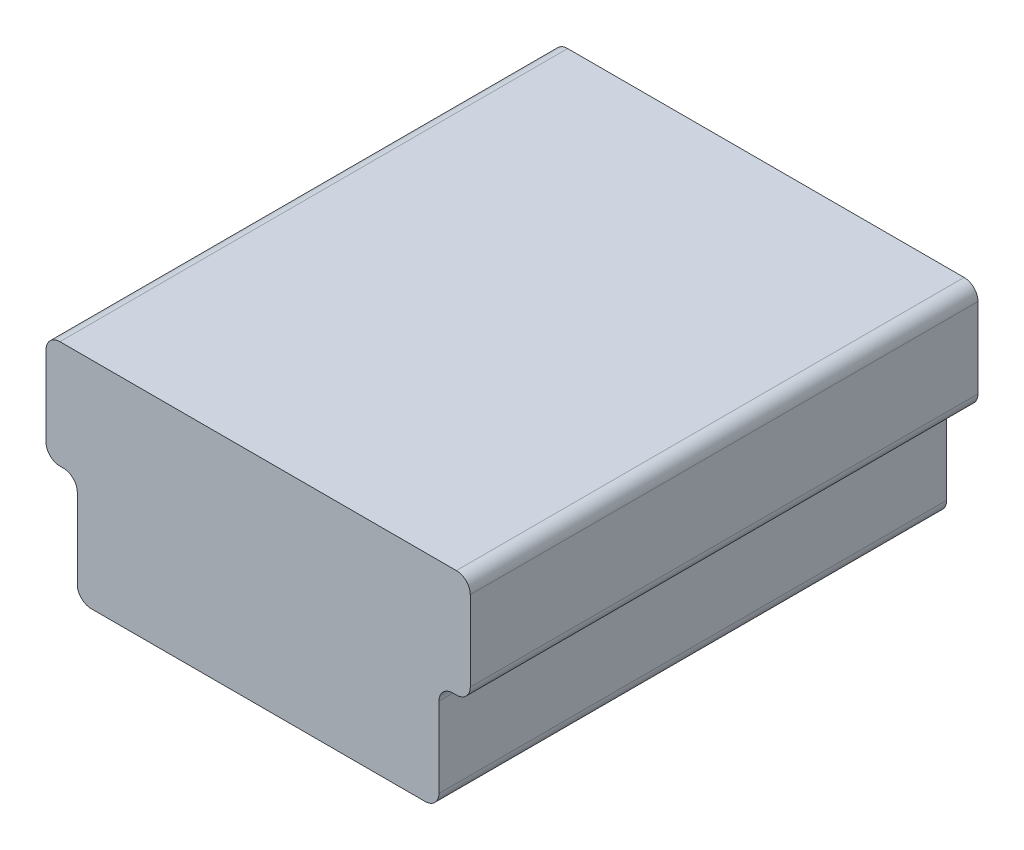
SolidWorks part; units mm, degrees
ref_plane "Front Plane" through (0, 0, 0) normal (0, 0, 1) x (1, 0, 0)
ref_plane "Top Plane" through (0, 0, 0) normal (0, 1, 0) x (1, 0, 0)
ref_plane "Right Plane" through (0, 0, 0) normal (1, 0, 0) x (0, 0, -1)
ref_plane "Plane1" through (0, 0, 0) normal (0, -1, 0) x (1, 0, 0)
sketch "Sketch1" plane through (0, 0, 0) normal (0, -1, 0) x (1, 0, 0)
  line L0 (-3.8735, 0) -> (3.8735, 0)
  line L1 (3.8735, 0) -> (3.8735, 9.271)
  line L2 (3.8735, 9.271) -> (-3.8735, 9.271)
  line L3 (-3.8735, 9.271) -> (-3.8735, 0)
extrude "Boss-Extrude1" add sketch "Sketch1" against normal blind 3.937
sketch "Sketch2" plane through (0, 0, 0) normal (0, 0, -1) x (-1, 0, 0)
  line L0 (-3.302, 0) -> (-3.302, 1.9685)
  line L1 (-3.302, 1.9685) -> (-3.8735, 1.9685)
  line L2 (-3.8735, 1.9685) -> (-3.8735, 0)
  line L3 (-3.8735, 0) -> (-3.302, 0)
extrude "Cut-Extrude1" cut sketch "Sketch2" against normal through all
sketch "Sketch3" plane through (0, 0, 0) normal (0, 0, -1) x (-1, 0, 0)
  line L0 (3.8735, 1.9685) -> (3.302, 1.9685)
  line L1 (3.302, 1.9685) -> (3.302, 0)
  line L2 (3.302, 0) -> (3.8735, 0)
  line L3 (3.8735, 0) -> (3.8735, 1.9685)
extrude "Cut-Extrude2" cut sketch "Sketch3" against normal through all
sketch "Sketch4" plane through (0, 0, 0) normal (0, 0, -1) x (-1, 0, 0)
  line L0 (3.4925, 2.3463) -> (3.4925, 3.556)
  line L1 (3.4925, 3.556) -> (-3.4925, 3.556)
  line L2 (-3.4925, 3.556) -> (-3.4925, 2.3463)
  line L3 (-2.921, 1.7145) -> (-2.921, 0.381)
  line L4 (-2.921, 0.381) -> (2.921, 0.381)
  line L5 (2.921, 0.381) -> (2.921, 1.7145)
  arc A0 (2.921, 1.7145) -> (3.4925, 2.3463) centre (3.556, 1.7145) cw
  arc A1 (-3.4925, 2.3463) -> (-2.921, 1.7145) centre (-3.556, 1.7145) cw
extrude "Cut-Extrude3" cut sketch "Sketch4" against normal blind 8.89
sketch "Sketch5" plane through (0, 0, 8.89) normal (0, 0, -1) x (-1, 0, 0)
  line L0 (-2.2225, 1.016) -> (-2.2225, 2.54)
  line L1 (-2.2225, 2.54) -> (2.2225, 2.54)
  line L2 (2.2225, 2.54) -> (2.2225, 1.016)
  line L3 (2.2225, 1.016) -> (-2.2225, 1.016)
extrude "Boss-Extrude2" add sketch "Sketch5" along normal blind 8.001
chamfer "Chamfer1" distance 0.508 angle 45 2 edges at (2.2225, 1.016, 4.8895) (-2.2225, 1.016, 4.8895)
fillet "Fillet1" radius 0.254 8 edges at (3.8735, 3.937, 4.6355) (3.8735, 1.9685, 4.6355) (-3.302, 0, 4.6355) (3.302, 1.9685, 4.6355) (-3.8735, 3.937, 4.6355) (-3.302, 1.9685, 4.6355) (3.302, 0, 4.6355) (-3.8735, 1.9685, 4.6355) tangent propagation no
